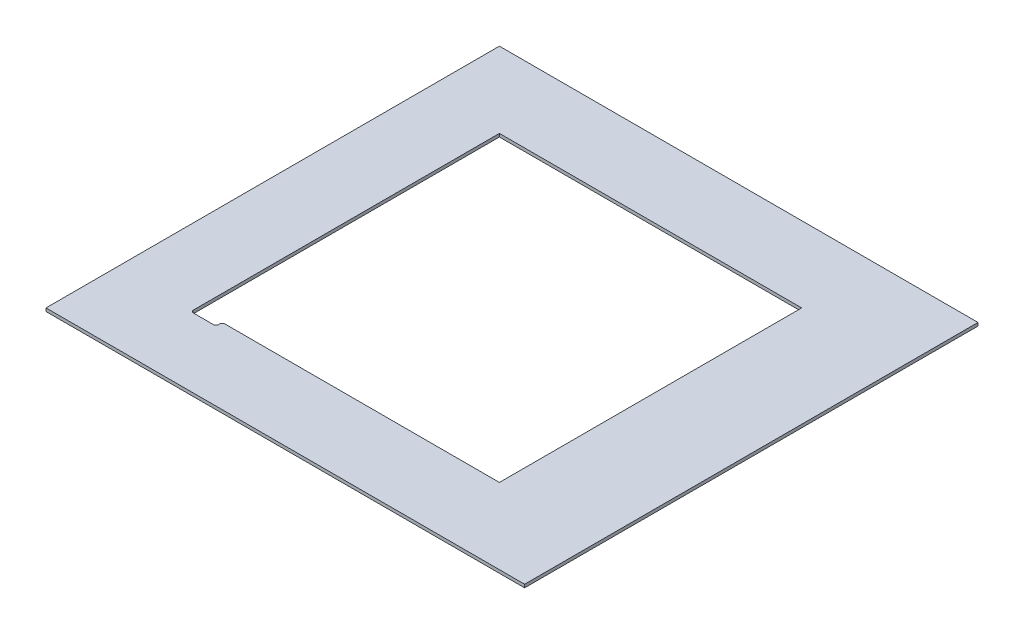
SolidWorks part; units mm, degrees
ref_plane "Front" through (0, 0, 0) normal (0, 0, 1) x (1, 0, 0)
ref_plane "Top" through (0, 0, 0) normal (0, 1, 0) x (1, 0, 0)
ref_plane "Right" through (0, 0, 0) normal (1, 0, 0) x (0, 0, -1)
sketch "Sketch1" plane through (0, 0, 0) normal (0, 1, 0) x (1, 0, 0)
  line L0 (-55, 0) -> (55, 0) construction
  line L1 (-242.5515, 228.6) -> (240.0485, 228.6)
  line L2 (-242.5515, 228.6) -> (-242.5515, -228.6)
  line L3 (-242.5515, -228.6) -> (240.0485, -228.6)
  line L4 (240.0485, 228.6) -> (240.0485, -228.6)
  line L5 (-242.5515, 228.6) -> (240.0485, -228.6) construction
  line L6 (-242.5515, -228.6) -> (240.0485, 228.6) construction
  line L7 (-166.3515, 152.4) -> (138.4485, 152.4)
  line L8 (-166.3515, 152.4) -> (-166.3515, -152.4)
  line L9 (-166.3515, -152.4) -> (138.4485, -152.4)
  line L10 (138.4485, 152.4) -> (138.4485, -152.4)
  line L11 (-166.3515, 152.4) -> (138.4485, -152.4) construction
  line L12 (-166.3515, -152.4) -> (138.4485, 152.4) construction
  line L13 (-160.0015, 146.05) -> (132.0985, 146.05)
  line L14 (-160.0015, 146.05) -> (-160.0015, -146.05)
  line L15 (-160.0015, -146.05) -> (132.0985, -146.05)
  line L16 (132.0985, 146.05) -> (132.0985, -146.05)
  line L17 (-160.0015, 146.05) -> (132.0985, -146.05) construction
  line L18 (-160.0015, -146.05) -> (132.0985, 146.05) construction
  line L19 (-166.3515, -152.4) -> (-140.9515, -152.4)
  line L20 (-166.3515, -152.4) -> (-166.3515, -158.75)
  line L21 (-166.3515, -158.75) -> (-140.9515, -158.75)
  line L22 (-140.9515, -152.4) -> (-140.9515, -158.75)
  point P0 (-1.2515, 0)
  point P6 (-44.5662, -1.1741)
  point P11 (-84.1987, 3.6789)
  point P21 (-13.9515, 0)
  point P22 (-13.9515, 0)
  point P23 (-1.2515, 0)
  dimension "D1" = 457.2
  dimension "D2" = 482.6
  dimension "D3" = 304.8
  dimension "D4" = 304.8
  dimension "D5" = 76.2
  dimension "D6" = 292.1
  dimension "D7" = 146.05
  dimension "D8" = 228.6
  dimension "D9" = 25.4
  dimension "D10" = 6.35
extrude "Boss-Extrude1" add sketch "Sketch1" along normal blind 3.175 contours L4 L1 L2 L3 L7 L10 L9 L8 region at (-1.2515, 0, -221.9522)
fillet "Fillet1" radius 2.54 3 edges at (-140.9515, 1.5875, 158.75) (-166.3515, 1.5875, 158.75) (-140.9515, 1.5875, 152.4)
